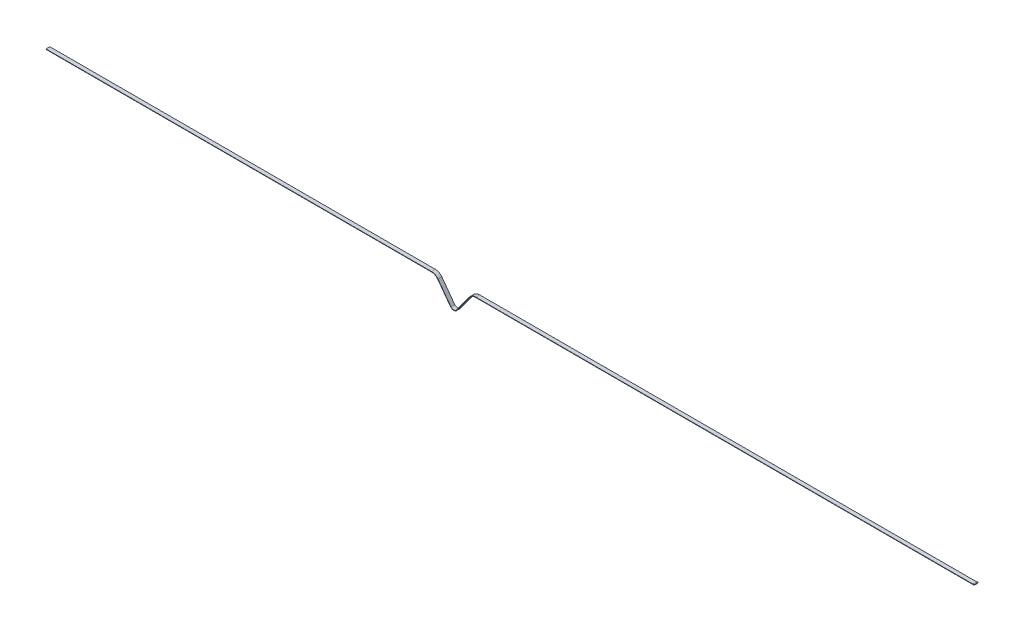
SolidWorks part; units mm, degrees
material "BUTYL"
ref_plane "Front Plane" through (0, 0, 0) normal (0, 0, 1) x (1, 0, 0)
ref_plane "Top Plane" through (0, 0, 0) normal (0, 1, 0) x (1, 0, 0)
ref_plane "Right Plane" through (0, 0, 0) normal (1, 0, 0) x (0, 0, -1)
sketch "Sketch1" plane through (0, 0, 0) normal (1, 0, 0) x (0, 0, -1)
  line L1 (0, 0) -> (6, 0)
  line L2 (0, 0) -> (0, 0.63)
  line L3 (0, 0.63) -> (6, 0.63)
  line L4 (6, 0) -> (6, 0.63)
  dimension "D1" = 0.63
  dimension "D2" = 6
sketch "Sketch2" plane through (0, 0, 0) normal (0, 0, 1) x (1, 0, 0)
  line L0 (0, 0) -> (-777.3151, 0)
  line L1 (-786.9478, -4.8779) -> (-806.96, -32.1359)
  line L2 (-816.8103, -32.1359) -> (-836.8225, -4.8779)
  line L3 (-846.4551, 0) -> (-1447.8, 0)
  arc A0 (-777.3151, 0) -> (-786.9478, -4.8779) centre (-777.3151, -11.95) ccw
  arc A1 (-806.96, -32.1359) -> (-816.8103, -32.1359) centre (-811.8851, -28.52) cw
  arc A2 (-836.8225, -4.8779) -> (-846.4551, 0) centre (-846.4551, -11.95) ccw
  circle A3 centre (-811.8851, -28.52) radius 8 construction
  circle A4 centre (-777.3151, -11.95) radius 11.95 construction
  circle A5 centre (-846.4551, -11.95) radius 11.95 construction
  dimension "D1" = 6.11
  dimension "D4" = 1447.8
sweep "Sweep1" add profiles "Sketch1" path "Sketch2"
sketch "Sketch3" plane through (0, 0, 0) normal (0, 0, 1) x (1, 0, 0)
  line L0 (0, 0.63) -> (-777.3151, 0.63) construction
  line L1 (-1.5, 0.63) -> (-1.5, 0)
  line L2 (0, 0) -> (-777.3151, 0) construction
  line L3 (-1.5, 0) -> (0, 0)
  line L4 (0, 0) -> (0, 0.63)
  arc A1 (0, 0.63) -> (-1.5, 0.63) centre (-0.75, 0.63) ccw
  dimension "D1" = 0.75
extrude "Boss-Extrude1" add sketch "Sketch3" against normal through all
pattern_curve "CrvPattern1" [suppressed] of bodies 102 driven by "Sketch2" parameters "D1"=2000, "D3"=2, "D2"=1, "D4"=10
